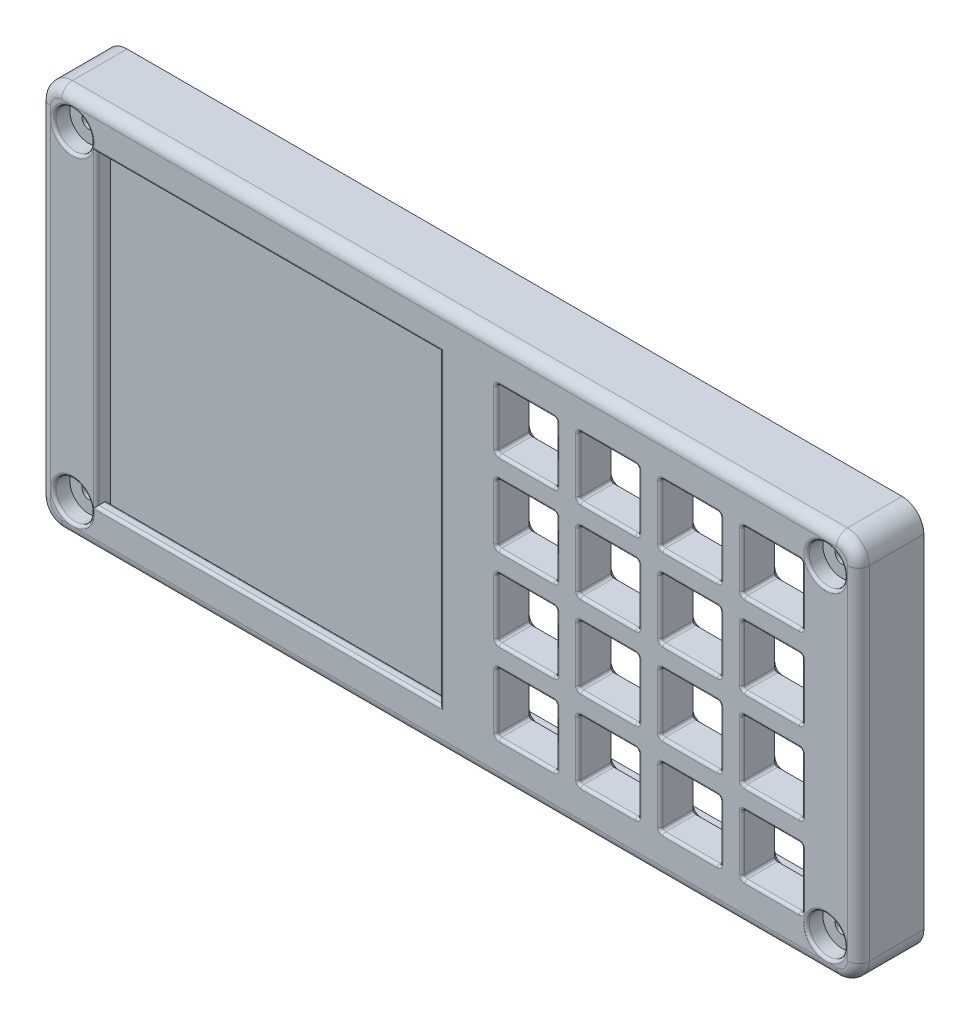
SolidWorks part; units mm, degrees
ref_plane "Front Plane" through (0, 0, 0) normal (0, 0, 1) x (1, 0, 0)
ref_plane "Top Plane" through (0, 0, 0) normal (0, 1, 0) x (1, 0, 0)
ref_plane "Right Plane" through (0, 0, 0) normal (1, 0, 0) x (0, 0, -1)
sketch "Sketch1" plane through (0, 0, 0) normal (0, 0, 1) x (1, 0, 0)
  line L1 (0, 0) -> (150, 0)
  line L2 (0, 0) -> (0, 70.75)
  line L3 (0, 70.75) -> (150, 70.75)
  line L4 (150, 0) -> (150, 70.75)
  dimension "D1" = 70.75
  dimension "D2" = 150
extrude "Boss-Extrude1" add sketch "Sketch1" along normal blind 7
sketch "Sketch2" plane through (0, 0, 7) normal (0, 0, 1) x (1, 0, 0)
  line L0 (150, 0) -> (150, 70.75) construction
  line L1 (141.93, 5.125) -> (81.43, 5.125)
  line L2 (141.93, 5.125) -> (141.93, 65.625)
  line L3 (141.93, 65.625) -> (81.43, 65.625)
  line L4 (81.43, 5.125) -> (81.43, 65.625)
  line L5 (0, 0) -> (150, 0) construction
  line L7 (128.68, 63.375) -> (139.68, 63.375)
  line L8 (128.68, 63.375) -> (128.68, 52.375)
  line L9 (128.68, 52.375) -> (139.68, 52.375)
  line L10 (139.68, 63.375) -> (139.68, 52.375)
  dimension "D1" = 60.5
  dimension "D2" = 60.5
  dimension "D3" = 8.07
  dimension "D4" = 5.125
  dimension "D5" = 11
  dimension "D6" = 11
  dimension "D7" = 2.25
  dimension "D8" = 2.25
extrude "Cut-Extrude2" cut sketch "Sketch2" against normal blind 7 contours L8 L7 L10 L9
fillet "Fillet1" radius 0.5 8 edges at (139.68, 63.375, 3.5) (139.68, 52.375, 3.5) (128.68, 52.375, 3.5) (128.68, 63.375, 3.5) (134.18, 52.375, 7) (128.68, 57.875, 7) (134.18, 63.375, 7) (139.68, 57.875, 7)
chamfer "Chamfer1" distance 1 angle 45 8 edges at (139.68, 57.875, 0) (134.18, 52.375, 0) (128.68, 57.875, 0) (128.8264, 52.5214, 0) (139.5336, 52.5214, 0) (128.8264, 63.2286, 0) (139.5336, 63.2286, 0) (134.18, 63.375, 0)
pattern_linear "LPattern1" count 4 spacing 15 along (-1, 0, 0) count 4 spacing 15 along (0, -1, 0) of "Cut-Extrude2", "Fillet1", "Chamfer1"
sketch "Sketch3" plane through (0, 0, 7) normal (0, 0, 1) x (1, 0, 0)
  line L0 (0, 70.75) -> (0, 0) construction
  line L1 (10.32, 65.505) -> (73.36, 65.505)
  line L2 (10.32, 65.505) -> (10.32, 5.245)
  line L3 (10.32, 5.245) -> (73.36, 5.245)
  line L4 (73.36, 65.505) -> (73.36, 5.245)
  line L6 (150, 0) -> (150, 70.75) construction
  line L7 (0, 0) -> (150, 0) construction
  line L8 (150, 70.75) -> (0, 70.75) construction
  dimension "D1" = 10.32
  dimension "D2" = 76.64
  dimension "D3" = 5.245
  dimension "D4" = 5.245
extrude "Cut-Extrude3" cut sketch "Sketch3" against normal blind 2.65
sketch "Sketch4" plane through (0, 65.505, 0) normal (0, -1, 0) x (-1, 0, 0)
  line L0 (-73.36, -4.35) -> (-73.36, -7) construction
  line L1 (-10.32, -7) -> (-73.36, -7)
  line L2 (-10.32, -7) -> (-10.32, -5)
  line L3 (-10.32, -5) -> (-73.36, -5)
  line L4 (-73.36, -7) -> (-73.36, -5)
  dimension "D1" = 2
extrude "Boss-Extrude2" add sketch "Sketch4" along normal blind 2
sketch "Sketch5" plane through (0, 5.245, 0) normal (0, 1, 0) x (1, 0, 0)
  line L0 (73.36, -4.35) -> (73.36, -7) construction
  line L1 (10.32, -7) -> (73.36, -7)
  line L2 (10.32, -7) -> (10.32, -5)
  line L3 (10.32, -5) -> (73.36, -5)
  line L4 (73.36, -7) -> (73.36, -5)
  dimension "D1" = 2
extrude "Boss-Extrude4" add sketch "Sketch5" along normal blind 2
fillet "Fillet3" radius 0.5 4 edges at (41.84, 7.245, 7) (73.36, 35.375, 7) (10.32, 35.375, 7) (41.84, 63.505, 7)
fillet "Fillet4" radius 0.5 2 edges at (41.84, 7.245, 5) (41.84, 63.505, 5)
fillet "Fillet5" radius 0.25 2 edges at (41.84, 65.505, 5) (41.84, 5.245, 5)
sketch "Sketch6" plane through (0, 0, 0) normal (0, 0, -1) x (-1, 0, 0)
  line L0 (0, 0) -> (-150, 0) construction
  line L1 (-2.5, 2.5) -> (-147.5, 2.5)
  line L2 (-2.5, 2.5) -> (-2.5, 68.25)
  line L3 (-2.5, 68.25) -> (-147.5, 68.25)
  line L4 (-147.5, 2.5) -> (-147.5, 68.25)
  line L5 (0, 70.75) -> (0, 0) construction
  line L6 (-150, 70.75) -> (0, 70.75) construction
  line L7 (-150, 0) -> (-150, 70.75) construction
  line L9 (0, 0) -> (-150, 0)
  line L10 (0, 0) -> (0, 70.75)
  line L11 (0, 70.75) -> (-150, 70.75)
  line L12 (-150, 0) -> (-150, 70.75)
  dimension "D1" = 2.5
  dimension "D2" = 2.5
  dimension "D3" = 2.5
  dimension "D4" = 2.5
extrude "Boss-Extrude5" add sketch "Sketch6" along normal blind 5
sketch "Sketch7" plane through (0, 0, -5) normal (0, 0, -1) x (-1, 0, 0)
  line L0 (-2.5, 2.5) -> (-2.5, 68.25) construction
  line L1 (-2.5, 52.62) -> (0, 52.62)
  line L2 (-2.5, 52.62) -> (-2.5, 40.62)
  line L3 (-2.5, 40.62) -> (0, 40.62)
  line L4 (0, 52.62) -> (0, 40.62)
  line L5 (0, 0) -> (0, 70.75) construction
  line L6 (0, 70.75) -> (-150, 70.75) construction
  dimension "D1" = 18.13
  dimension "D2" = 12
extrude "Cut-Extrude5" cut sketch "Sketch7" against normal blind 5
fillet "Fillet6" radius 1 5 edges at (0, 52.62, -2.5) (1.25, 52.62, 0) (0, 40.62, -2.5) (1.25, 40.62, 0) (0, 46.62, 0)
fillet "Fillet9" radius 4 4 edges at (150, 70.75, 1) (150, 0, 1) (0, 0, 1) (0, 70.75, 1)
fillet "Fillet10" radius 2 8 edges at (1.1716, 69.5784, 7) (148.8284, 69.5784, 7) (148.8284, 1.1716, 7) (1.1716, 1.1716, 7) (150, 35.375, 7) (75, 70.75, 7) (75, 0, 7) (0, 35.375, 7)
sketch "Sketch8" plane through (0, 0, 0) normal (0, 0, -1) x (-1, 0, 0)
  line L0 (-2.5, 52.62) -> (-2.5, 68.25) construction
  line L1 (-5.62, 52.62) -> (-2.5, 52.62)
  line L2 (-5.62, 52.62) -> (-5.62, 55.12)
  line L3 (-5.62, 55.12) -> (-2.5, 55.12)
  line L4 (-2.5, 52.62) -> (-2.5, 55.12)
  line L5 (-2.5, 40.62) -> (-5.62, 40.62)
  line L6 (-2.5, 40.62) -> (-2.5, 38.12)
  line L7 (-2.5, 38.12) -> (-5.62, 38.12)
  line L8 (-5.62, 40.62) -> (-5.62, 38.12)
  line L9 (-1, 52.62) -> (-2.5, 52.62) construction
  line L10 (-2.5, 2.5) -> (-2.5, 40.62) construction
  line L11 (-2.5, 40.62) -> (-1, 40.62) construction
  dimension "D1" = 3.12
  dimension "D2" = 2.5
  dimension "D3" = 0
  dimension "D4" = 0
  dimension "D5" = 3.12
  dimension "D6" = 2.5
  dimension "D7" = 0
  dimension "D8" = 0
extrude "Boss-Extrude6" add sketch "Sketch8" along normal blind 5
fillet "Fillet11" radius 1 2 edges at (4.06, 52.62, 0) (4.06, 40.62, 0)
fillet "Fillet12" radius 1 6 edges at (4.06, 38.12, 0) (5.62, 38.12, -2.5) (5.62, 39.87, 0) (5.62, 55.12, -2.5) (5.62, 53.37, 0) (4.06, 55.12, 0)
sketch "Sketch9" plane through (0, 0, 7) normal (0, 0, 1) x (1, 0, 0)
  line L0 (4, 70.75) -> (146, 70.75) construction
  line L1 (0, 4) -> (0, 66.75) construction
  line L2 (146, 0) -> (4, 0) construction
  line L3 (150, 66.75) -> (150, 4) construction
  circle A0 centre (6, 64.75) radius 1.25
  circle A1 centre (144, 64.75) radius 1.25
  circle A2 centre (144, 6) radius 1.25
  circle A3 centre (6, 6) radius 1.25
  dimension "D1" = 2.5
  dimension "D2" = 2.5
  dimension "D3" = 2.5
  dimension "D4" = 2.5
  dimension "D5" = 6
  dimension "D6" = 6
  dimension "D7" = 6
  dimension "D8" = 6
  dimension "D9" = 6
  dimension "D10" = 6
  dimension "D11" = 6
  dimension "D12" = 6
extrude "Cut-Extrude6" cut sketch "Sketch9" against normal blind 15
sketch "Sketch10" plane through (0, 0, 7) normal (0, 0, 1) x (1, 0, 0)
  circle A0 centre (6, 64.75) radius 3.5
  circle A1 centre (144, 64.75) radius 3.5
  circle A2 centre (144, 6) radius 3.5
  circle A3 centre (6, 6) radius 3.5
  dimension "D1" = 7
  dimension "D2" = 7
  dimension "D3" = 7
  dimension "D4" = 7
extrude "Cut-Extrude7" cut sketch "Sketch10" against normal blind 3
fillet "Fillet13" radius 1 13 edges at (2.5, 68.25, -2.5) (2.5, 2.5, -2.5) (75, 68.25, 0) (75, 2.5, 0) (2.5, 55.12, -3) (2.5, 55.4129, -0.2929) (2.5, 38.12, -3) (2.5, 37.8271, -0.2929) (2.5, 62.185, 0) (2.5, 19.81, 0) (147.5, 2.5, -2.5) (147.5, 68.25, -2.5) (147.5, 35.375, 0)
sketch "Sketch11" plane through (0, 0, 0) normal (0, 0, -1) x (-1, 0, 0)
  line L0 (0, 53.62) -> (0, 66.75) construction
  line L1 (-4, 70.75) -> (-146, 70.75) construction
  line L2 (0, 4) -> (0, 39.62) construction
  line L3 (-146, 0) -> (-4, 0) construction
  circle A0 centre (-23.56, 59.12) radius 2.25
  circle A1 centre (-22.29, 10.86) radius 2.25
  circle A2 centre (-71.36, 43.92) radius 2
  circle A3 centre (-71.36, 15.94) radius 2
  dimension "D1" = 4.5
  dimension "D2" = 4.5
  dimension "D3" = 4
  dimension "D4" = 4
  dimension "D5" = 23.56
  dimension "D6" = 11.63
  dimension "D7" = 22.29
  dimension "D8" = 10.86
  dimension "D9" = 15.94
  dimension "D10" = 71.36
  dimension "D11" = 71.36
  dimension "D12" = 26.83
extrude "Boss-Extrude7" add sketch "Sketch11" along normal blind 6.6
fillet "Fillet14" radius 0.4 4 edges at (69.36, 15.94, -6.6) (20.04, 10.86, -6.6) (69.36, 43.92, -6.6) (21.31, 59.12, -6.6)
sketch "Sketch13" plane through (0, 0, 0) normal (0, 0, -1) x (-1, 0, 0)
  circle A1 centre (-23.56, 59.12) radius 3.25
  circle A3 centre (-22.29, 10.86) radius 3.25
  circle A5 centre (-23.56, 59.12) radius 1.85 construction
  circle A6 centre (-22.29, 10.86) radius 1.85 construction
  circle A8 centre (-71.36, 15.94) radius 3.25
  circle A10 centre (-71.36, 43.92) radius 3.25
  dimension "D1" = 6.5
  dimension "D2" = 6.5
  dimension "D3" = 6.5
  dimension "D4" = 6.5
  dimension "D6" = 0
  dimension "D7" = 0
extrude "Boss-Extrude8" add sketch "Sketch13" along normal blind 4.8
fillet "Fillet15" radius 1 8 edges at (19.04, 10.86, 0) (20.31, 59.12, 0) (19.04, 10.86, -4.8) (20.31, 59.12, -4.8) (68.11, 43.92, -4.8) (68.11, 43.92, 0) (68.11, 15.94, -4.8) (68.11, 15.94, 0)
fillet "Fillet16" radius 0.5 4 edges at (147.5, 6, 7) (147.5, 64.75, 7) (9.5, 64.75, 7) (9.5, 6, 7)
